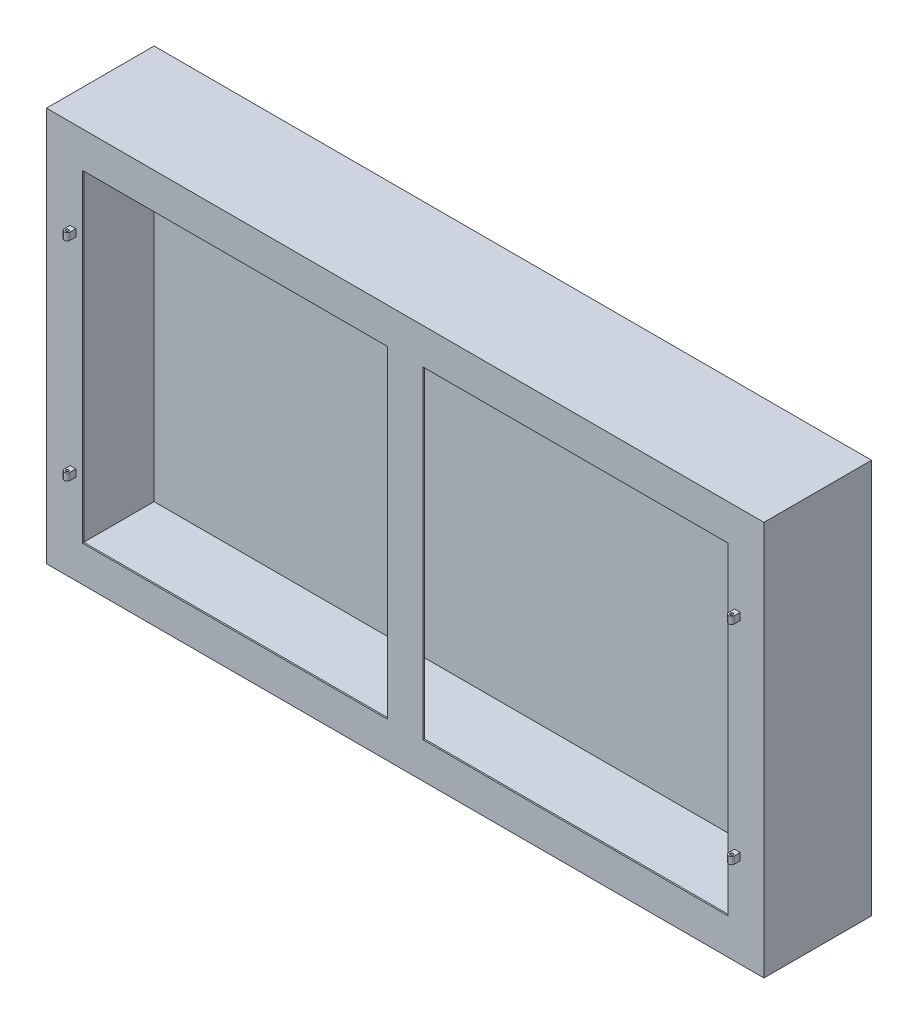
SolidWorks part; units mm, degrees
material "1345 Alloy"
ref_plane "FRONT" through (0, 0, 0) normal (0, 0, 1) x (1, 0, 0)
ref_plane "TOP" through (0, 0, 0) normal (0, 1, 0) x (1, 0, 0)
ref_plane "RIGHT" through (0, 0, 0) normal (1, 0, 0) x (0, 0, -1)
other "Configuration Table"
sketch "Sketch1" plane through (0, 0, 0) normal (0, 0, 1) x (1, 0, 0)
  line L1 (0, 0) -> (-1000, 0)
  line L2 (0, 0) -> (0, 550)
  line L3 (0, 550) -> (-1000, 550)
  line L4 (-1000, 0) -> (-1000, 550)
  dimension "D1" = 550
  dimension "D2" = 1000
extrude "Base-Extrude" add sketch "Sketch1" along normal blind 150
sketch "Sketch2" plane through (0, 0, 150) normal (0, 0, 1) x (1, 0, 0)
  line L8 (-50, 50) -> (-50, 500)
  line L9 (-50, 500) -> (-950, 500)
  line L10 (-950, 500) -> (-950, 50)
  line L11 (-950, 50) -> (-50, 50)
  line L12 (-50, 50) -> (-50, 500)
  line L13 (-50, 500) -> (-950, 500)
  line L14 (-950, 500) -> (-950, 50)
  line L15 (-950, 50) -> (-50, 50)
  dimension "D1" = 50
extrude "Cut-Extrude1" cut sketch "Sketch2" against normal offset from surface (148 mm away) 2 up to face at (-500, 275, 0)
shell "Shell3" thickness 2 removed face at (-500, 275, 2)
sketch "Sketch3" plane through (0, 0, 150) normal (0, 0, 1) x (1, 0, 0)
  line L0 (-500, 50) -> (-500, 500) construction
  line L1 (-950, 50) -> (-50, 50) construction
  line L2 (-50, 500) -> (-950, 500) construction
  line L4 (-475, 50) -> (-525, 50)
  line L5 (-475, 50) -> (-475, 500)
  line L6 (-475, 500) -> (-525, 500)
  line L7 (-525, 50) -> (-525, 500)
  dimension "D1" = 50
extrude "Boss-Extrude1" add sketch "Sketch3" against normal blind 2
ref_plane "Plane1" through (0, 125, 0) normal (0, -1, 0) x (1, 0, 0)
sketch "Sketch4" plane through (0, 125, 0) normal (0, -1, 0) x (1, 0, 0)
  line L0 (-41, 150) -> (-33, 150)
  line L1 (-33, 150) -> (-33, 158)
  line L2 (-41, 150) -> (-41, 158)
  line L3 (-1000, 150) -> (0, 150) construction
  arc A0 (-41, 158) -> (-33, 158) centre (-37, 158) cw
  circle A1 centre (-37, 158) radius 2
  dimension "D2" = 4
  dimension "D1" = 8
  dimension "D3" = 8
  dimension "D4" = 9
extrude "Boss-Extrude2" add sketch "Sketch4" against normal blind 10
ref_plane "Plane2" through (-500, 0, 0) normal (-1, 0, 0) x (0, 0, 1)
mirror "Mirror1" about plane through (-500, 0, 0) normal (-1, 0, 0) of "Boss-Extrude2"
ref_plane "Plane3" through (0, 275, 0) normal (0, -1, 0) x (1, 0, 0)
mirror "Mirror2" about plane through (0, 275, 0) normal (0, -1, 0) of "Boss-Extrude2", "Mirror1"
sketch "Sketch5" plane through (0, 0, 0) normal (0, 0, 1) x (1, 0, 0)
  line L1 (0, 550) -> (40, 550)
  line L2 (0, 550) -> (0, 590)
  line L3 (0, 590) -> (40, 590)
  line L4 (40, 550) -> (40, 590)
  dimension "D1" = 40
surface "Surface-Plane1" sketch "Sketch5"
